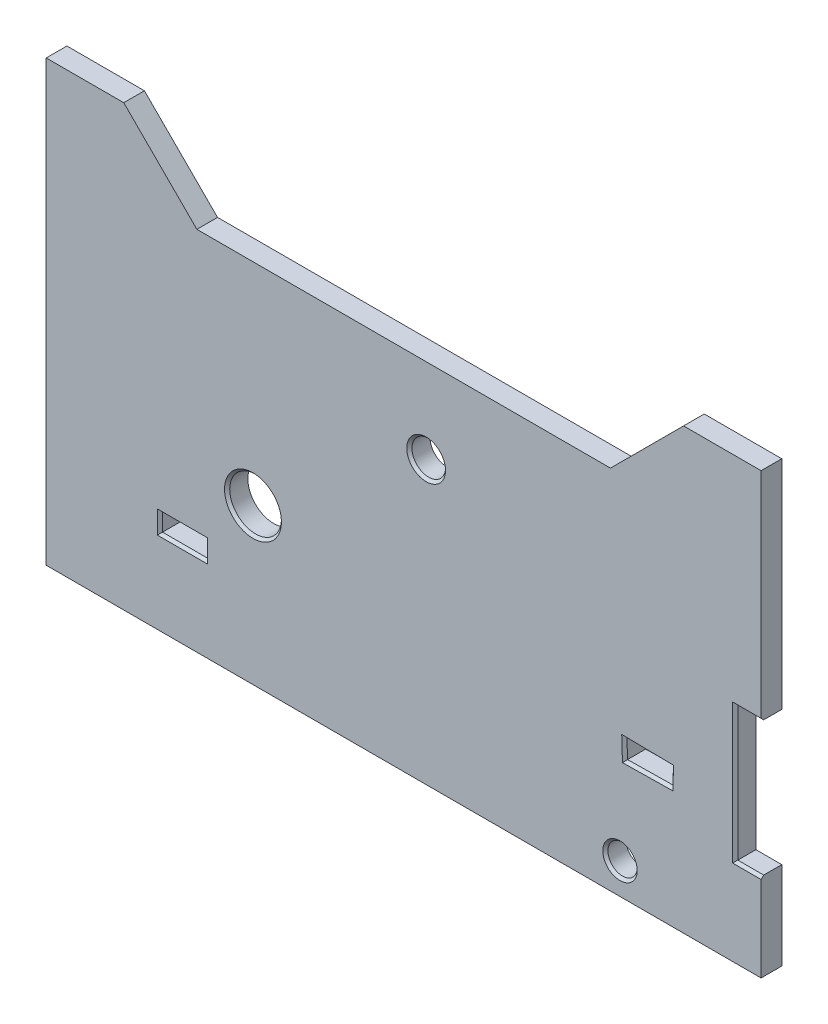
SolidWorks part; units mm, degrees
ref_plane "Front Plane" through (0, 0, 0) normal (0, 0, 1) x (1, 0, 0)
ref_plane "Top Plane" through (0, 0, 0) normal (0, 1, 0) x (1, 0, 0)
ref_plane "Right Plane" through (0, 0, 0) normal (1, 0, 0) x (0, 0, -1)
sketch "Sketch1" plane through (0, 0, 0) normal (0, 0, 1) x (1, 0, 0)
  line L2 (-86, -30) -> (-86, 30)
  line L6 (52.3, 13) -> (47.3, 13)
  line L7 (47.3, 13) -> (47.3, -13)
  line L8 (47.3, -13) -> (52.3, -13)
  line L11 (52.3, 30) -> (52.3, 13)
  line L12 (52.3, -13) -> (52.3, -30)
  line L23 (52.3, 30) -> (-86, 30)
  line L24 (25.8505, -3.1759) -> (34.8495, -3.3118)
  line L25 (25.8505, -3.1759) -> (25.9628, -6.8241)
  line L26 (25.9628, -6.8241) -> (34.7372, -6.6882)
  line L27 (34.8495, -3.3118) -> (34.7372, -6.6882)
  line L28 (25.9067, -5) -> (34.7933, -5) construction
  line L29 (30.35, -3.2438) -> (30.35, -6.7562) construction
  line L30 (-86, -30) -> (52.3, -30)
  line L31 (-55.3, -12) -> (-64, -12) construction
  line L32 (-64, -10.3) -> (-55.3, -10.3)
  line L33 (-64, -10.3) -> (-64, -13.7)
  line L34 (-64, -13.7) -> (-55.3, -13.7)
  line L35 (-55.3, -10.3) -> (-55.3, -13.7)
  line L36 (-52.65, -10.3) -> (-52.65, -13.7) construction
  circle A3 centre (-46, 0) radius 5
  circle A4 centre (25, -24) radius 2.83
  circle A5 centre (-12.5, 24.5) radius 3.25
  point P1 (-12, 0)
  dimension "D5" = 10
  dimension "D17" = 5.66
  dimension "D25" = 6.5
  dimension "D1" = 40
  dimension "D8" = 26
  dimension "D13" = 9
  dimension "D14" = 3.65
  dimension "D18" = 111
  dimension "D27" = 33.5
  dimension "D28" = 24.5
  dimension "D6" = 5
  dimension "D4" = 24
  dimension "D7" = 116.35
  dimension "D9" = 60
  dimension "D3" = 138.3
  dimension "D10" = 5
  dimension "D11" = 12
  dimension "D12" = 33.35
extrude "Boss-Extrude1" add sketch "Sketch1" along normal mid plane 4
sketch "Sketch2" plane through (0, 0, 0) normal (0, 0, 1) x (1, 0, 0)
  line L0 (-86, 30) -> (52.3, 30)
  line L1 (52.3, 30) -> (52.3, 55)
  line L2 (52.3, 55) -> (37.3, 55)
  line L3 (37.3, 55) -> (23.1579, 40.8579)
  line L4 (23.1579, 40.8579) -> (-56.8579, 40.8579)
  line L5 (-56.8579, 40.8579) -> (-71, 55)
  line L6 (-71, 55) -> (-86, 55)
  line L7 (-86, 55) -> (-86, 30)
  dimension "D1" = 25
  dimension "D2" = 15
  dimension "D3" = 20
  dimension "D4" = 135
extrude "Boss-Extrude2" add sketch "Sketch2" along normal mid plane 4
sketch "Sketch3" plane through (0, 0, 2) normal (0, 0, 1) x (1, 0, 0)
  line L0 (25.9067, -5) -> (34.7933, -5) construction
  line L1 (25.8505, -3.1759) -> (25.9628, -6.8241) construction
  line L2 (34.7372, -6.6882) -> (34.8495, -3.3118) construction
  line L3 (30.35, -3.2438) -> (30.35, -6.7562) construction
  line L4 (34.8495, -3.3118) -> (25.8505, -3.1759) construction
  line L5 (25.9628, -6.8241) -> (34.7372, -6.6882) construction
  line L6 (-64, -12) -> (-55.3, -12) construction
  line L7 (-64, -10.3) -> (-64, -13.7) construction
  line L8 (-55.3, -13.7) -> (-55.3, -10.3) construction
  line L9 (-59.65, -10.3) -> (-59.65, -13.7) construction
  line L10 (-55.3, -10.3) -> (-64, -10.3) construction
  line L11 (-64, -13.7) -> (-55.3, -13.7) construction
sketch "Sketch4" plane through (47.3, 0, 0) normal (1, 0, 0) x (0, 0, -1)
  line L0 (-2, 0) -> (2, 0) construction
  line L1 (-2, -13) -> (-2, 13) construction
  line L2 (2, -13) -> (2, 13) construction
chamfer "Chamfer1" distance 0.5 angle 45 14 edges at (49.8, -13, 2) (49.8, 13, 2) (47.3, 0, 2) (27.83, -24, 2) (30.35, -6.7562, 2) (25.9067, -5, 2) (30.35, -3.2438, 2) (34.7933, -5, 2) (-55.3, -12, 2) (-59.65, -13.7, 2) (-64, -12, 2) (-59.65, -10.3, 2) (-41, 0, 2) (-9.25, 24.5, 2)
equation "\"back_boost\"= 7"
equation "\"D18@Sketch1\"=\"back_boost\"+104.00mm"
equation "\"D1@Sketch1\"=33.00mm+\"back_boost\""
equation "\"D7@Sketch1\"=109.35mm+\"back_boost\""
equation "\"D3@Sketch1\"=131.30mm+\"back_boost\""
equation "\"D12@Sketch1\"=\"back_boost\"+26.35mm"
equation "\"pin_hole_height\"=9"
equation "\"D13@Sketch1\"=\"pin_hole_height\""
equation "\"pin_hole_width\"=3.65"
equation "\"D14@Sketch1\"=\"pin_hole_width\""
